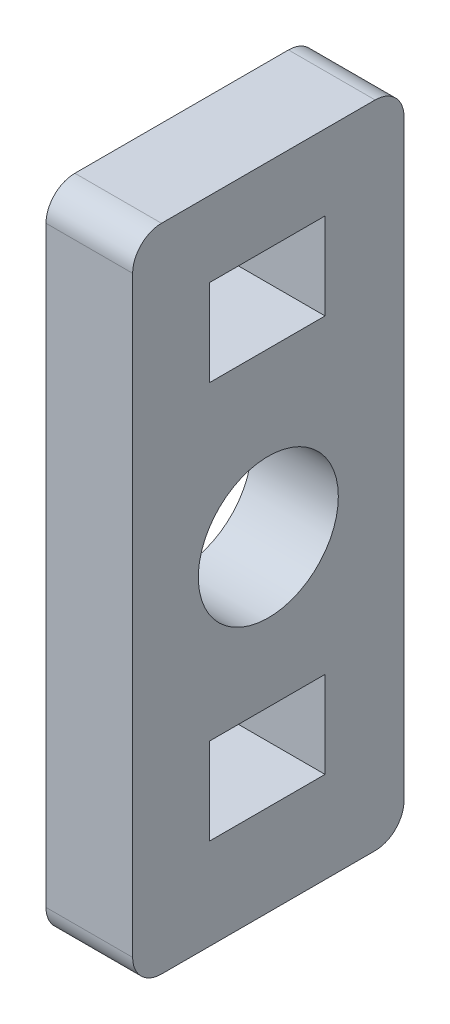
SolidWorks part; units mm, degrees
ref_plane "Front Plane" through (0, 0, 0) normal (0, 0, 1) x (1, 0, 0)
ref_plane "Top Plane" through (0, 0, 0) normal (0, 1, 0) x (1, 0, 0)
ref_plane "Right Plane" through (0, 0, 0) normal (1, 0, 0) x (0, 0, -1)
sketch "Sketch1" plane through (0, 0, 0) normal (1, 0, 0) x (0, 0, -1)
  line L0 (-2.3157, -5.4181) -> (1.6843, -5.4181)
  line L1 (-4.9796, 10.9429) -> (4.4183, 10.9429)
  line L2 (-4.9796, 10.9429) -> (-4.9796, -11.5748)
  line L3 (-4.9796, -11.5748) -> (4.4183, -11.5748)
  line L4 (4.4183, 10.9429) -> (4.4183, -11.5748)
  line L5 (1.6843, -5.4181) -> (1.6843, -8.4181)
  line L6 (1.6843, -8.4181) -> (-2.3157, -8.4181)
  line L7 (-2.3157, -8.4181) -> (-2.3157, -5.4181)
  line L8 (-2.3157, 8.3319) -> (-2.3157, 5.3319)
  line L9 (-2.3157, 5.3319) -> (1.6843, 5.3319)
  line L10 (1.6843, 5.3319) -> (1.6843, 8.3319)
  line L11 (1.6843, 8.3319) -> (-2.3157, 8.3319)
  line L12 (-0.2806, 10.9429) -> (-0.2806, -11.5748) construction
  line L13 (4.4183, -0.316) -> (-4.9796, -0.316) construction
  circle A0 centre (-0.2806, -0.316) radius 2.425
  dimension "D2" = 4.85
  dimension "D1" = 10.75
extrude "Boss-Extrude1" add sketch "Sketch1" along normal blind 3
ref_axis "Axis2" through (3, 10.9429, 0.2806) along (0, -1, 0)
ref_axis "Axis3" through (3, -0.316, -4.4183) along (0, 0, 1)
ref_point "Point1"
ref_axis "Axis4" through (3, -0.316, 0.2806) along (-1, 0, 0)
fillet "Fillet1" radius 1 4 edges at (1.5, -11.5748, 4.9796) (1.5, -11.5748, -4.4183) (1.5, 10.9429, 4.9796) (1.5, 10.9429, -4.4183)
